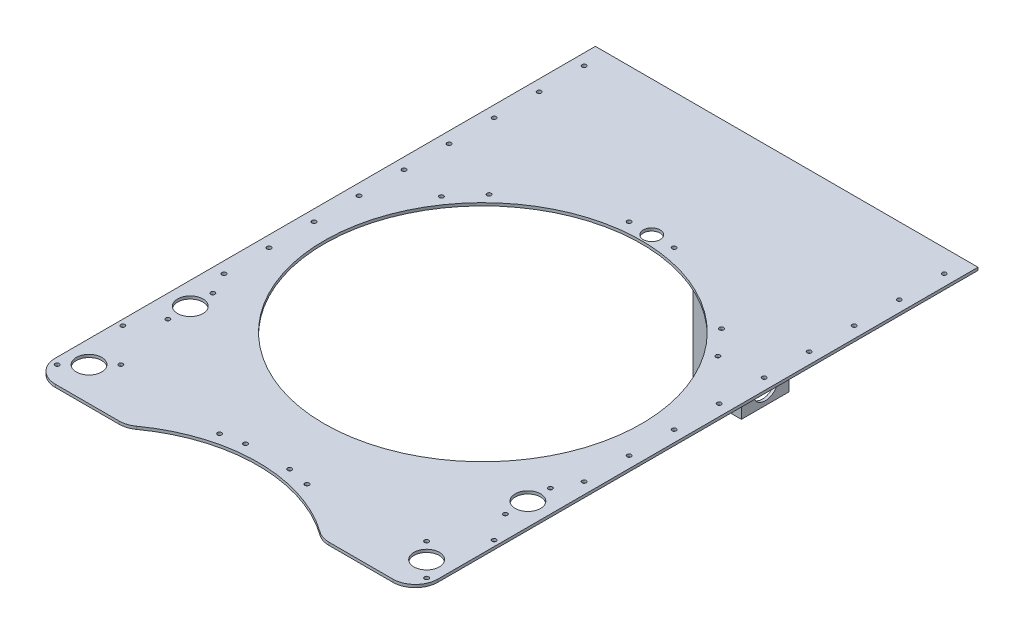
SolidWorks part; units mm, degrees
material "6063-T1"
ref_plane "Front Plane" through (0, 0, 0) normal (0, 0, 1) x (1, 0, 0)
ref_plane "Top Plane" through (0, 0, 0) normal (0, 1, 0) x (1, 0, 0)
ref_plane "Right Plane" through (0, 0, 0) normal (1, 0, 0) x (0, 0, -1)
sketch "Sketch1" plane through (0, 0, 0) normal (0, 1, 0) x (1, 0, 0)
  line L1 (-215.9, 342.9) -> (215.9, 342.9)
  line L2 (-215.9, 342.9) -> (-215.9, -342.9)
  line L3 (-215.9, -342.9) -> (215.9, -342.9)
  line L4 (215.9, 342.9) -> (215.9, -342.9)
  line L5 (-215.9, 342.9) -> (215.9, -342.9) construction
  line L6 (-215.9, -342.9) -> (215.9, 342.9) construction
  point P0 (0, 0)
  dimension "D1" = 431.8
  dimension "D2" = 685.8
extrude "Boss-Extrude1" add sketch "Sketch1" along normal blind 3.175
sketch "Sketch2" plane through (0, 3.175, 0) normal (0, 1, 0) x (1, 0, 0)
  line L0 (0, -342.9) -> (0, 342.9) construction
  line L1 (-215.9, -342.9) -> (215.9, -342.9) construction
  line L2 (215.9, 342.9) -> (-215.9, 342.9) construction
  line L3 (-215.9, 342.9) -> (-215.9, -342.9) construction
  line L4 (-208.4605, -322.7605) -> (-190.5, -304.8) construction
  line L5 (-193.1461, -304.8) -> (-215.9, -304.8) construction
  circle A0 centre (-190.5, -304.8) radius 14.3129
  circle A1 centre (-190.5, -190.5) radius 14.3129
  circle A3 centre (190.5, -190.5) radius 14.3129
  circle A4 centre (190.5, -190.5) radius 25.4 construction
  circle A5 centre (-190.5, -190.5) radius 25.4 construction
  circle A6 centre (190.5, -215.9) radius 2.3813
  circle A7 centre (190.5, -165.1) radius 2.3813
  circle A8 centre (-190.5, -215.9) radius 2.3813
  circle A9 centre (-190.5, -165.1) radius 2.3813
  circle A10 centre (-190.5, -304.8) radius 25.4 construction
  circle A11 centre (-208.4605, -322.7605) radius 2.3813
  circle A15 centre (-172.5395, -286.8395) radius 2.3813
  circle A16 centre (172.5395, -286.8395) radius 2.3813
  circle A17 centre (208.4605, -322.7605) radius 2.3813
  circle A18 centre (190.5, -304.8) radius 14.3129
  point P33 (-190.5, -304.8)
  point P34 (-190.5, -304.8)
  dimension "D1" = 28.6258
  dimension "D2" = 28.6258
  dimension "D6" = 50.8
  dimension "D7" = 50.8
  dimension "D8" = 4.7625
  dimension "D9" = 4.7625
  dimension "D10" = 4.7625
  dimension "D11" = 4.7625
  dimension "D12" = 50.8
  dimension "D13" = 4.7625
  dimension "D3" = 38.1
  dimension "D4" = 114.3
  dimension "D5" = 25.4
  dimension "D15" = 45
  dimension "D14" = 2
extrude "Cut-Extrude1" cut sketch "Sketch2" against normal through all
sketch "Sketch3" plane through (0, 0, 0) normal (0, -1, 0) x (-1, 0, 0)
  line L1 (29.8706, 270.2084) -> (-24.7394, 270.2084)
  line L2 (29.8706, 270.2084) -> (29.8706, 216.2334)
  line L3 (29.8706, 216.2334) -> (-24.7394, 216.2334)
  line L4 (-24.7394, 270.2084) -> (-24.7394, 216.2334)
  line L5 (29.8706, 270.2084) -> (-24.7394, 216.2334) construction
  line L6 (29.8706, 216.2334) -> (-24.7394, 270.2084) construction
  point P0 (2.5656, 243.2209)
  dimension "D1" = 53.975
  dimension "D2" = 54.61
extrude "Boss-Extrude2" add sketch "Sketch3" along normal blind 203.2
fillet "Fillet1" [suppressed] radius 20.32
sketch "Sketch4" plane through (0, -203.2, 0) normal (0, -1, 0) x (-1, 0, 0)
  line L0 (-24.7394, 216.2334) -> (29.8706, 216.2334) construction
  line L1 (26.6956, 267.0334) -> (-21.5644, 267.0334)
  line L2 (26.6956, 267.0334) -> (26.6956, 219.4084)
  line L3 (26.6956, 219.4084) -> (-21.5644, 219.4084)
  line L4 (-21.5644, 267.0334) -> (-21.5644, 219.4084)
  line L5 (26.6956, 267.0334) -> (-21.5644, 219.4084) construction
  line L6 (26.6956, 219.4084) -> (-21.5644, 267.0334) construction
  line L7 (29.8706, 270.2084) -> (-24.7394, 270.2084) construction
  line L8 (29.8706, 216.2334) -> (29.8706, 270.2084) construction
  line L9 (-24.7394, 270.2084) -> (-24.7394, 216.2334) construction
  point P0 (2.5656, 243.2209)
  dimension "D1" = 3.175
  dimension "D2" = 3.175
  dimension "D3" = 3.175
  dimension "D4" = 3.175
extrude "Cut-Extrude2" cut sketch "Sketch4" against normal blind 203.2
sketch "Sketch5" plane through (-29.8706, 0, 0) normal (-1, 0, 0) x (0, 0, 1)
  line L0 (-216.2334, -203.2) -> (-216.2334, 0) construction
  line L1 (-216.2334, -203.2) -> (-270.2084, -203.2) construction
  circle A0 centre (-243.2209, -184.15) radius 14.2875
  dimension "D1" = 28.575
  dimension "D2" = 26.9875
  dimension "D3" = 19.05
extrude "Cut-Extrude3" cut sketch "Sketch5" against normal blind 203.2
sketch "Sketch6" plane through (0, 3.175, 0) normal (0, 1, 0) x (1, 0, 0)
  circle A0 centre (0, -50.8) radius 179.07
  dimension "D1" = 358.14
  dimension "D2" = 50.8
extrude "Cut-Extrude4" cut sketch "Sketch6" against normal through all
sketch "Sketch8" plane through (0, 3.175, 0) normal (0, 1, 0) x (1, 0, 0)
  circle A0 centre (0, 139.7) radius 9.525
  circle A2 centre (0, 139.7) radius 25.4 construction
  circle A3 centre (25.4, 139.7) radius 2.3813
  circle A4 centre (-25.4, 139.7) radius 2.3813
  dimension "D1" = 19.05
  dimension "D3" = 50.8
  dimension "D4" = 4.7625
  dimension "D5" = 4.7625
  dimension "D2" = 139.7
extrude "Cut-Extrude6" cut sketch "Sketch8" against normal through all
fillet "Fillet2" radius 25.4 2 edges at (215.9, 1.5875, 342.9) (-215.9, 1.5875, 342.9)
sketch "Sketch10" plane through (0, 3.175, 0) normal (0, 1, 0) x (1, 0, 0)
  line L0 (-215.9, 342.9) -> (-215.9, -317.5) construction
  line L1 (215.9, -317.5) -> (215.9, 342.9) construction
  circle A0 centre (-190.5, 215.9) radius 14.3129
  circle A1 centre (190.5, 215.9) radius 14.3129
  circle A2 centre (-190.5, 215.9) radius 25.4 construction
  circle A3 centre (190.5, 215.9) radius 25.4 construction
  circle A4 centre (190.5, 190.5) radius 2.3813
  circle A5 centre (190.5, 241.3) radius 2.3813
  circle A6 centre (-190.5, 190.5) radius 2.3813
  circle A7 centre (-190.5, 241.3) radius 2.3813
  circle A8 centre (190.5, -190.5) radius 14.3129 construction
  circle A9 centre (-190.5, -190.5) radius 14.3129 construction
  dimension "D1" = 28.6258
  dimension "D2" = 50.8
  dimension "D3" = 28.6258
  dimension "D4" = 50.8
  dimension "D5" = 4.7625
  dimension "D6" = 4.7625
  dimension "D7" = 4.7625
  dimension "D8" = 4.7625
  dimension "D9" = 25.4
  dimension "D10" = 25.4
  dimension "D11" = 406.4
  dimension "D12" = 406.4
extrude "Cut-Extrude8" [suppressed] cut sketch "Sketch10" against normal through all
sketch "Sketch11" plane through (0, 3.175, 0) normal (0, 1, 0) x (1, 0, 0)
  line L0 (0, -50.8) -> (156.0485, 58.4663) construction
  line L6 (0, 0) -> (0, 139.7) construction
  circle A0 centre (0, -50.8) radius 179.07
  circle A1 centre (0, -50.8) radius 179.07 construction
  circle A2 centre (0, -50.8) radius 184.15
  circle A3 centre (0, -50.8) radius 215.9
  circle A4 centre (156.0485, 58.4663) radius 2.3813
  circle A5 centre (131.1838, 87.3342) radius 2.3813
  circle A6 centre (0, -50.8) radius 190.5 construction
  circle A7 centre (-131.1838, 87.3342) radius 2.3813
  circle A8 centre (-156.0485, 58.4663) radius 2.3813
  dimension "D1" = 368.3
  dimension "D6" = 431.8
  dimension "D7" = 381
  dimension "D9" = 4.7625
  dimension "D10" = 4.7625
  dimension "D2" = 55
  dimension "D8" = 38.1
extrude "Cut-Extrude9" cut sketch "Sketch11" against normal through all contours A4 | A5 | A7 | A8 region at (156.0485, 3.175, -58.4663) region at (131.1838, 3.175, -87.3342) region at (-131.1838, 3.175, -87.3342) region at (-156.0485, 3.175, -58.4663)
sketch "Sketch13" plane through (0, 3.175, 0) normal (0, 1, 0) x (1, 0, 0)
  line L0 (-215.9, 342.9) -> (-215.9, -317.5) construction
  line L1 (215.9, 342.9) -> (-215.9, 342.9) construction
  line L2 (0, -342.9) -> (0, 342.9) construction
  line L3 (-190.5, -342.9) -> (190.5, -342.9) construction
  circle A0 centre (-203.2, 317.5) radius 2.3813
  circle A1 centre (-203.2, 266.7) radius 2.3813
  circle A2 centre (-203.2, 215.9) radius 2.3813
  circle A3 centre (-203.2, 165.1) radius 2.3813
  circle A4 centre (-203.2, 114.3) radius 2.3813
  circle A5 centre (-203.2, 63.5) radius 2.3813
  circle A6 centre (-203.2, 12.7) radius 2.3813
  circle A7 centre (-203.2, -38.1) radius 2.3813
  circle A8 centre (-203.2, -88.9) radius 2.3813
  circle A9 centre (-203.2, -139.7) radius 2.3813
  circle A10 centre (203.2, -139.7) radius 2.3813
  circle A11 centre (203.2, 12.7) radius 2.3813
  circle A12 centre (203.2, 63.5) radius 2.3813
  circle A13 centre (203.2, 114.3) radius 2.3813
  circle A14 centre (203.2, 165.1) radius 2.3813
  circle A15 centre (203.2, 266.7) radius 2.3813
  circle A16 centre (203.2, 317.5) radius 2.3813
  circle A17 centre (-25.4, -330.2) radius 2.4664
  circle A20 centre (-50.8, -330.2) radius 2.3078
  circle A21 centre (50.8, -330.2) radius 2.3078
  circle A22 centre (25.4, -330.2) radius 2.4664
  circle A23 centre (203.2, -88.9) radius 2.3813
  circle A24 centre (203.2, -38.1) radius 2.3813
  circle A25 centre (203.2, 215.9) radius 2.3813
  dimension "D1" = 4.7625
  dimension "D2" = 12.7
  dimension "D3" = 25.4
  dimension "D5" = 25.4
  dimension "D6" = 50.8
  dimension "D7" = 12.7
  dimension "D8" = 12.7
  dimension "D4" = 10
extrude "Cut-Extrude10" cut sketch "Sketch13" against normal through all
sketch "Sketch14" plane through (0, 3.175, 0) normal (0, 1, 0) x (1, 0, 0)
  line L0 (215.9, -317.5) -> (215.9, 342.9) construction
  line L1 (0, -342.9) -> (0, -229.87) construction
  line L2 (-190.5, -342.9) -> (190.5, -342.9) construction
  circle A0 centre (209.55, -247.65) radius 2.3813
  circle A2 centre (0, -50.8) radius 179.07 construction
  circle A3 centre (-209.55, -247.65) radius 2.3813
  circle A4 centre (190.5, -304.8) radius 14.3129 construction
  dimension "D1" = 57.15
  dimension "D3" = 4.7625
  dimension "D2" = 6.35
extrude "Cut-Extrude11" cut sketch "Sketch14" against normal through all
sketch "Sketch16" plane through (0, 3.175, 0) normal (0, 1, 0) x (1, 0, 0)
  line L0 (215.9, -317.5) -> (215.9, 342.9) construction
  line L1 (-215.9, 342.9) -> (215.9, 342.9)
  line L2 (-215.9, 342.9) -> (-215.9, 292.1)
  line L3 (-215.9, 292.1) -> (215.9, 292.1)
  line L4 (215.9, 342.9) -> (215.9, 292.1)
  dimension "D1" = 50.8
extrude "Cut-Extrude13" cut sketch "Sketch16" against normal through all
sketch "Sketch17" plane through (0, 0, 0) normal (0, -1, 0) x (-1, 0, 0)
  line L0 (0, -482.6) -> (0, 3.1553) construction
  line L1 (0, -482.6) -> (24.8652, -293.7298) construction
  line L2 (0, -482.6) -> (49.305, -298.5911) construction
  circle A0 centre (0, -482.6) radius 177.8
  circle A1 centre (0, -482.6) radius 190.5 construction
  circle A2 centre (24.8652, -293.7298) radius 2.3813
  circle A3 centre (49.305, -298.5911) radius 2.3813
  circle A4 centre (-24.8652, -293.7298) radius 2.3813
  circle A5 centre (-49.305, -298.5911) radius 2.3813
  dimension "D1" = 355.6
  dimension "D3" = 381
  dimension "D6" = 4.7625
  dimension "D7" = 4.7625
  dimension "D2" = 482.6
  dimension "D4" = 7.5
  dimension "D5" = 15
extrude "Cut-Extrude14" cut sketch "Sketch17" against normal through all
fillet "Fillet3" radius 25.4 2 edges at (109.9852, 1.5875, 342.9) (-109.9852, 1.5875, 342.9)
